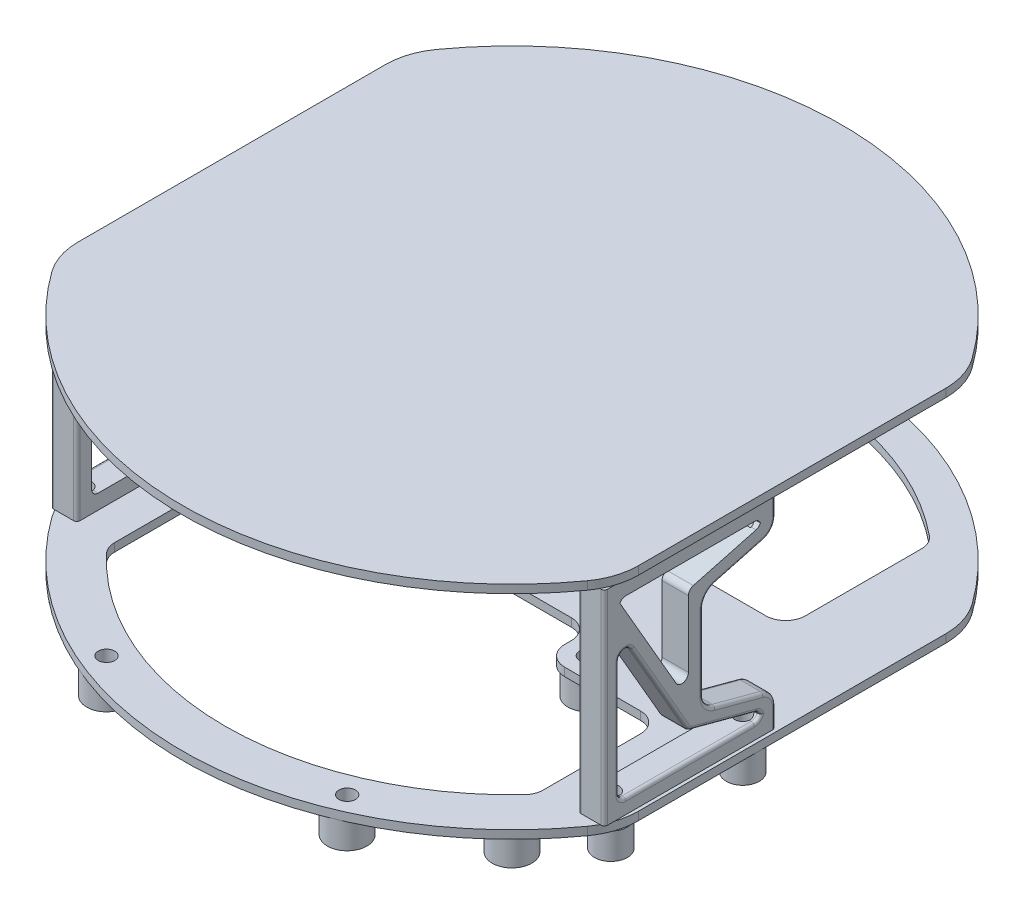
SolidWorks part; units mm, degrees
ref_plane "Front" through (0, 0, 0) normal (0, 0, 1) x (1, 0, 0)
ref_plane "Top" through (0, 0, 0) normal (0, 1, 0) x (1, 0, 0)
ref_plane "Right" through (0, 0, 0) normal (1, 0, 0) x (0, 0, -1)
sketch "Sketch1" plane through (0, 0, 0) normal (0, 1, 0) x (1, 0, 0)
  line L0 (0, 71.1393) -> (0, -87.7098) construction
  line L1 (-42.5, 26.3391) -> (-42.5, -26.3391)
  line L2 (42.5, 26.3391) -> (42.5, -26.3391)
  arc A0 (-42.5, -26.3391) -> (42.5, -26.3391) centre (0, 0) ccw
  arc A1 (42.5, 26.3391) -> (-42.5, 26.3391) centre (0, 0) ccw
  dimension "D1" = 100
  dimension "D2" = 85
extrude "Boss-Extrude1" add sketch "Sketch1" along normal blind 1.25
sketch "Sketch2" plane through (0, 0, 0) normal (0, -1, 0) x (1, 0, 0)
  line L0 (0, 45.5144) -> (0, -63.1722) construction
  line L1 (-51.2989, 0) -> (55.2567, 0) construction
  circle A0 centre (-33, 33) radius 3
  circle A2 centre (-33, 33) radius 1.25
  circle A4 centre (-33, -33) radius 1.25
  circle A5 centre (-33, -33) radius 3
  circle A6 centre (33, -33) radius 3
  circle A7 centre (33, -33) radius 1.25
  circle A8 centre (33, 33) radius 1.25
  circle A9 centre (33, 33) radius 3
  dimension "D3" = 2.5
  dimension "D4" = 6
  dimension "D1" = 66
  dimension "D2" = 66
extrude "Boss-Extrude2" add sketch "Sketch2" along normal blind 4
fillet "Fillet1" radius 10 4 edges at (-42.5, 0.625, -26.3391) (-42.5, 0.625, 26.3391) (42.5, 0.625, -26.3391) (42.5, 0.625, 26.3391)
sketch "Sketch3" plane through (0, 1.25, 0) normal (0, 1, 0) x (1, 0, 0)
  line L0 (0, 58.0627) -> (0, -62.1815) construction
  line L1 (-18.25, -6.75) -> (18.25, -6.75) construction
  line L2 (-18.25, -6.75) -> (-18.25, -43.25) construction
  line L3 (-18.25, -43.25) -> (18.25, -43.25) construction
  line L4 (18.25, -6.75) -> (18.25, -43.25) construction
  line L5 (-18.25, -6.75) -> (18.25, -43.25) construction
  line L6 (-18.25, -43.25) -> (18.25, -6.75) construction
  circle A0 centre (-18.25, -6.75) radius 1.25
  circle A1 centre (18.25, -6.75) radius 1.25
  circle A2 centre (18.25, -43.25) radius 1.25
  circle A3 centre (-18.25, -43.25) radius 1.25
  circle A4 centre (-40, -5) radius 1.25
  circle A5 centre (-40, -25) radius 1.25
  circle A6 centre (40, -25) radius 1.25
  circle A7 centre (40, -5) radius 1.25
  point P0 (0, -25)
  dimension "D1" = 2.5
  dimension "D2" = 36.5
  dimension "D3" = 25
  dimension "D4" = 20
  dimension "D5" = 80
  dimension "D6" = 0
sketch "Sketch4" plane through (0, 0, 0) normal (0, -1, 0) x (1, 0, 0)
  circle A0 centre (-18.25, 43.25) radius 3
  circle A1 centre (18.25, 43.25) radius 3
  circle A2 centre (18.25, 6.75) radius 3
  circle A3 centre (-18.25, 6.75) radius 3
  circle A4 centre (-40, 25) radius 2.5
  circle A5 centre (-40, 5) radius 2.5
  circle A6 centre (40, 25) radius 2.5
  circle A7 centre (40, 5) radius 2.5
  dimension "D1" = 6
  dimension "D2" = 5
extrude "Boss-Extrude3" add sketch "Sketch4" along normal up to surface (4 mm away) up to face at (-33, -4, 30)
extrude "Cut-Extrude1" cut sketch "Sketch3" against normal through all
sketch "Sketch6" plane through (0, 0, 0) normal (0, -1, 0) x (1, 0, 0)
  line L0 (-29.5, -33.9816) -> (-29.5, -12)
  line L1 (-29.5, -12) -> (-3.5, -12)
  line L2 (29.5, -12) -> (29.5, -33.9816)
  line L3 (0, 0) -> (0, -57.2909) construction
  line L4 (-32.5, 28.9137) -> (-32.5, 10)
  line L5 (-32.5, 10) -> (-15, 10)
  line L6 (32.5, 10) -> (32.5, 28.9137)
  line L7 (-3.5, -12) -> (-3.5, -44.8637)
  line L8 (3.5, -12) -> (3.5, -44.8637)
  line L9 (3.5, -12) -> (29.5, -12)
  line L10 (15, 10) -> (32.5, 10)
  line L12 (-15, 10) -> (-15, 3)
  line L13 (-15, 3) -> (15, 3)
  line L14 (15, 10) -> (15, 3)
  arc A0 (-29.5, -33.9816) -> (-3.5, -44.8637) centre (0, 0) ccw
  arc A1 (-40.625, -29.1481) -> (40.625, -29.1481) centre (0, 0) ccw construction
  arc A2 (-32.5, 28.9137) -> (32.5, 28.9137) centre (0, 0) cw
  arc A3 (40.625, 29.1481) -> (-40.625, 29.1481) centre (0, 0) ccw construction
  arc A4 (3.5, -44.8637) -> (29.5, -33.9816) centre (0, 0) ccw
  point P25 (0.1983, 4.1637)
  point P26 (11.2697, 3.3939)
  dimension "D2" = 5
  dimension "D4" = 6.5
  dimension "D1" = 59
  dimension "D3" = 12
  dimension "D5" = 10
  dimension "D6" = 7
  dimension "D7" = 65
  dimension "D8" = 7
  dimension "D9" = 30
extrude "Cut-Extrude2" cut sketch "Sketch6" against normal through all
fillet "Fillet2" radius 3 16 edges at (-29.5, 0.625, -12) (-3.5, 0.625, -12) (-3.5, 0.625, -44.8637) (29.5, 0.625, -12) (29.5, 0.625, -33.9816) (3.5, 0.625, -44.8637) (3.5, 0.625, -12) (-29.5, 0.625, -33.9816) (32.5, 0.625, 28.9137) (-32.5, 0.625, 28.9137) (-32.5, 0.625, 10) (32.5, 0.625, 10) (15, 0.625, 3) (15, 0.625, 10) (-15, 0.625, 3) (-15, 0.625, 10)
ref_point "Point1"
ref_plane "Plane1" through (-40, 0, 0) normal (-1, 0, 0) x (0, 0, 1)
sketch "Sketch7" plane through (-40, 0, 0) normal (-1, 0, 0) x (0, 0, 1)
  line L0 (2, 1.25) -> (2, 6.25)
  line L1 (-23.3184, 1.25) -> (23.3184, 1.25) construction
  line L2 (2, 6.25) -> (13, 9.1974)
  line L3 (13, 9.1974) -> (13, 24.3026)
  line L4 (13, 24.3026) -> (2, 27.25)
  line L5 (2, 27.25) -> (2, 32.25)
  line L6 (2, 32.25) -> (28, 32.25)
  line L7 (28, 32.25) -> (28, 1.25)
  line L8 (28, 1.25) -> (2, 1.25)
  line L9 (4.25, 30) -> (25.75, 30)
  line L10 (25.75, 30) -> (25.75, 29.6575)
  line L11 (25.75, 3.5) -> (4.25, 3.5)
  line L12 (4.25, 3.5) -> (4.25, 4.5235)
  line L13 (4.25, 4.5235) -> (15.25, 7.471)
  line L14 (15.25, 11.471) -> (15.25, 26.029)
  line L15 (15.25, 26.029) -> (4.25, 28.9765)
  line L16 (4.25, 28.9765) -> (4.25, 30)
  line L17 (15.25, 7.471) -> (25.75, 25.6575)
  line L19 (25.75, 29.6575) -> (15.25, 11.471)
  line L21 (15.25, 7.471) -> (15.25, 26.029) construction
  line L22 (25.75, 25.6575) -> (25.75, 3.5)
  line L23 (25.75, 30) -> (25.75, 3.5) construction
  dimension "D1" = 2
  dimension "D2" = 26
  dimension "D3" = 15
  dimension "D4" = 15
  dimension "D5" = 15
  dimension "D6" = 5
  dimension "D7" = 31
  dimension "D9" = 2
  dimension "D10" = 30
  dimension "D8" = 2.25
extrude "Boss-Extrude4" add sketch "Sketch7" along normal mid plane 4 separate body
fillet "Fillet3" radius 2.5 4 edges at (-40, 6.25, 2) (-40, 9.1974, 13) (-40, 24.3026, 13) (-40, 27.25, 2)
fillet "Fillet4" radius 1 11 edges at (-40, 25.6575, 25.75) (-40, 7.471, 15.25) (-40, 4.5235, 4.25) (-40, 3.5, 25.75) (-40, 3.5, 4.25) (-40, 11.471, 15.25) (-40, 30, 4.25) (-40, 28.9765, 4.25) (-40, 30, 25.75) (-40, 29.6575, 25.75) (-40, 26.029, 15.25)
fillet "Fillet5" radius 0.5 29 edges at (-38, 16.75, 28) (-38, 2.7908, 2) (-38, 5.8536, 2.5166) (-38, 7.7237, 7.5) (-38, 9.5939, 12.4834) (-38, 16.75, 13) (-38, 23.9061, 12.4834) (-38, 25.7763, 7.5) (-38, 27.6464, 2.5166) (-38, 30.7092, 2) (-42, 2.7908, 2) (-42, 5.8536, 2.5166) (-42, 7.7237, 7.5) (-42, 9.5939, 12.4834) (-42, 16.75, 13) (-42, 23.9061, 12.4834) (-42, 25.7763, 7.5) (-42, 27.6464, 2.5166) (-42, 30.7092, 2) (-42, 16.75, 28) (-42, 3.6718, 4.6896) (-42, 4.5042, 4.5863) (-42, 6.0429, 9.9205) (-42, 7.5363, 15.1998) (-42, 15.1276, 19.6705) (-42, 22.8914, 25.0088) (-42, 13.2127, 25.75) (-42, 3.7929, 25.4571) (-42, 3.5, 15)
sketch "Sketch8" plane through (0, 1.25, 0) normal (0, -1, 0) x (1, 0, 0)
  circle A0 centre (-40, 5) radius 1.25 construction
  circle A1 centre (-40, 25) radius 1.25 construction
  circle A2 centre (-40, 5) radius 1.25
  circle A3 centre (-40, 25) radius 1.25
extrude "Cut-Extrude3" cut sketch "Sketch8" against normal blind 3.5
extrude "Cut-Extrude4" cut sketch "Sketch8<3>" along normal blind 3.5 from surface starting at face at (-40, 32.25, 15)
sketch "Sketch8<3>" plane through (0, 1.25, 0) normal (0, -1, 0) x (1, 0, 0) same geometry as "Sketch8"
mirror "Mirror1" about plane through (0, 0, 0) normal (1, 0, 0) of bodies 109
sketch "Sketch9" plane through (0, 32.25, 0) normal (0, 1, 0) x (1, 0, 0)
  line L0 (-42.5, 23.3184) -> (-42.5, -23.3184) construction
  line L1 (42.5, -23.3184) -> (42.5, 23.3184) construction
  line L2 (-42.5, 23.3184) -> (-42.5, -23.3184)
  line L3 (42.5, -23.3184) -> (42.5, 23.3184)
  arc A0 (40.625, 29.1481) -> (-40.625, 29.1481) centre (0, 0) ccw construction
  arc A1 (-40.625, 29.1481) -> (-42.5, 23.3184) centre (-32.5, 23.3184) ccw construction
  arc A2 (-42.5, -23.3184) -> (-40.625, -29.1481) centre (-32.5, -23.3184) ccw construction
  arc A3 (-40.625, -29.1481) -> (40.625, -29.1481) centre (0, 0) ccw construction
  arc A4 (40.625, -29.1481) -> (42.5, -23.3184) centre (32.5, -23.3184) ccw construction
  arc A5 (42.5, 23.3184) -> (40.625, 29.1481) centre (32.5, 23.3184) ccw construction
  arc A6 (-40.625, 29.1481) -> (-42.5, 23.3184) centre (-32.5, 23.3184) ccw
  arc A7 (-42.5, -23.3184) -> (-40.625, -29.1481) centre (-32.5, -23.3184) ccw
  arc A8 (-40.625, -29.1481) -> (40.625, -29.1481) centre (0, 0) ccw
  arc A9 (40.625, -29.1481) -> (42.5, -23.3184) centre (32.5, -23.3184) ccw
  arc A10 (42.5, 23.3184) -> (40.625, 29.1481) centre (32.5, 23.3184) ccw
  arc A11 (40.625, 29.1481) -> (-40.625, 29.1481) centre (0, 0) ccw
extrude "Boss-Extrude6" add sketch "Sketch9" along normal blind 1.25 separate body
equation "\"D5@Sketch7\"=\"D4@Sketch7\""
